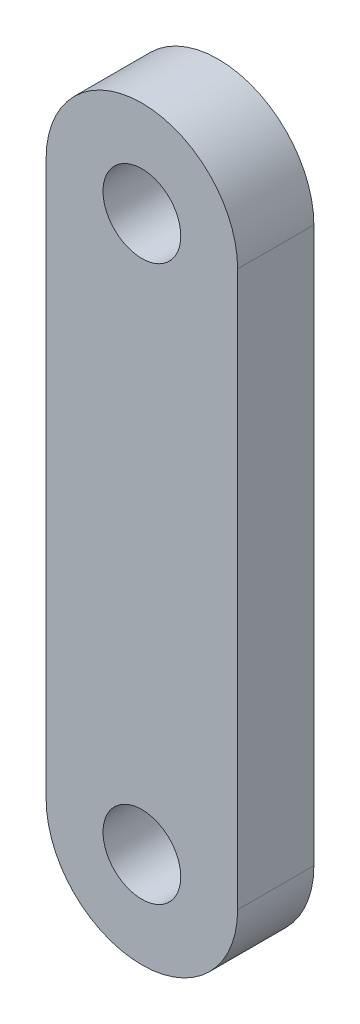
SolidWorks part; units mm, degrees
ref_plane "Front Plane" through (0, 0, 0) normal (0, 0, 1) x (1, 0, 0)
ref_plane "Top Plane" through (0, 0, 0) normal (0, 1, 0) x (1, 0, 0)
ref_plane "Right Plane" through (0, 0, 0) normal (1, 0, 0) x (0, 0, -1)
sketch "Sketch1" plane through (0, 0, 0) normal (0, 0, 1) x (1, 0, 0)
  line L0 (0, 23.114) -> (0, -23.114) construction
  line L1 (7.9756, 23.114) -> (7.9756, -23.114)
  line L2 (-7.9756, 23.114) -> (-7.9756, -23.114)
  arc A0 (7.9756, 23.114) -> (-7.9756, 23.114) centre (0, 23.114) ccw
  arc A1 (-7.9756, -23.114) -> (7.9756, -23.114) centre (0, -23.114) ccw
  circle A2 centre (0, 23.114) radius 3.2385
  circle A3 centre (0, -23.114) radius 3.2385
  point P3 (0, 0)
  point P12 (0, 0)
  dimension "D1" = 6.477
  dimension "D2" = 6.477
  dimension "D3" = 46.228
  dimension "D4" = 15.9512
extrude "Boss-Extrude1" add sketch "Sketch1" along normal blind 6.35
